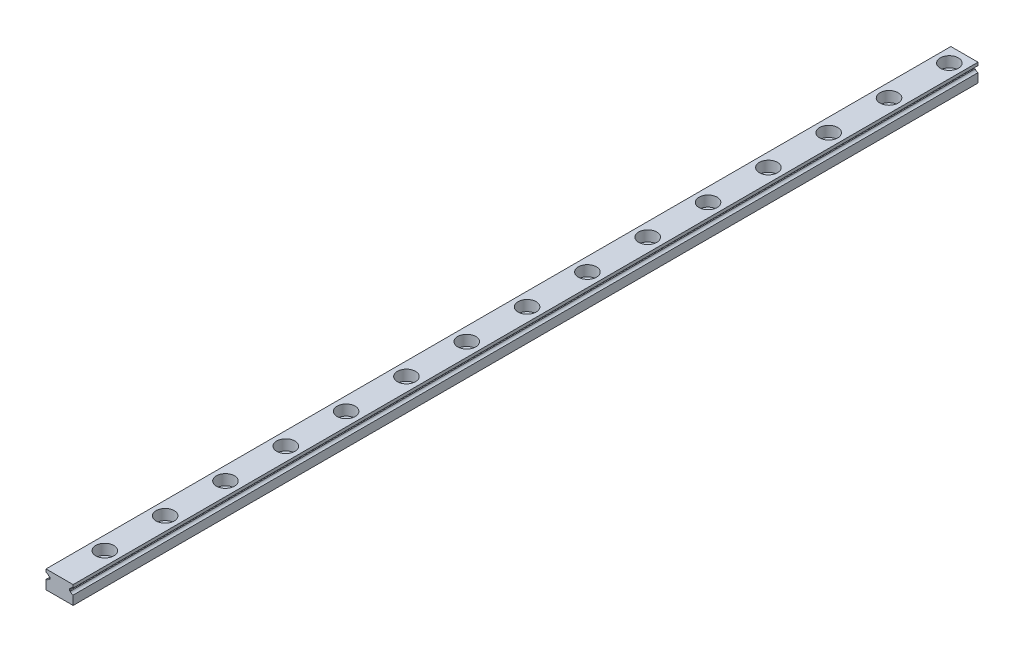
SolidWorks part; units mm, degrees
ref_plane "Спереди" through (0, 0, 0) normal (0, 0, 1) x (1, 0, 0)
ref_plane "Сверху" through (0, 0, 0) normal (0, 1, 0) x (1, 0, 0)
ref_plane "Справа" through (0, 0, 0) normal (1, 0, 0) x (0, 0, -1)
sketch "Sketch1" plane through (0, 0, 0) normal (0, 0, 1) x (1, 0, 0)
  line L0 (0, 0) -> (0, 5.7299) construction
  line L1 (-4.5, -3) -> (4.5, -3)
  line L2 (-4.5, -3) -> (-4.5, 0)
  line L3 (-4.5, 3) -> (4.5, 3)
  line L4 (4.5, -3) -> (4.5, 0)
  line L5 (-4.5, -3) -> (4.5, 3) construction
  line L6 (-4.5, 3) -> (4.5, -3) construction
  line L7 (-4.5, 2) -> (-4.5, 3)
  line L8 (-3.564, 0.648) -> (-3.2351, 0.648)
  line L9 (3.564, 0.648) -> (3.2351, 0.648)
  line L10 (-3.564, 1.352) -> (-3.2351, 1.352)
  line L11 (-3.2351, 0.648) -> (-3.2351, 1.352)
  line L12 (3.2351, 0.648) -> (3.2351, 1.352)
  line L13 (3.564, 1.352) -> (3.2351, 1.352)
  line L14 (4.5, 2) -> (4.5, 3)
  arc A0 (-3.564, 1.352) -> (-4.5, 2) centre (-4.5, 1) ccw
  arc A1 (-4.5, 0) -> (-3.564, 0.648) centre (-4.5, 1) ccw
  arc A2 (4.5, 0) -> (3.564, 0.648) centre (4.5, 1) cw
  arc A3 (3.564, 1.352) -> (4.5, 2) centre (4.5, 1) cw
  point P0 (0, 0)
  dimension "D3" = 1
  dimension "D1" = 9
  dimension "D2" = 6
  dimension "D4" = 2
extrude "Extrude1" add sketch "Sketch1" along normal blind 300
sketch "Sketch2" plane through (0, 3, 0) normal (0, 1, 0) x (1, 0, 0)
  line L0 (4.5, 0) -> (-4.5, 0) construction
  circle A0 centre (0, -5) radius 1.75
  circle A1 centre (0, -5) radius 3
  dimension "D1" = 3.5
  dimension "D2" = 6
  dimension "D3" = 5
extrude "Extrude2" cut sketch "Sketch2" against normal blind 3.5 contours A1
extrude "Extrude3" cut sketch "Sketch" against normal through all contours A0
sketch "Sketch" plane through (0, 3, 0) normal (0, 1, 0) x (1, 0, 0) same geometry as "Sketch2"
pattern_linear "LPattern1" count 15 spacing 20 along (0, 0, 1) of "Extrude2", "Extrude3"
sketch "草图1" plane through (0, 3, 0) normal (0, 1, 0) x (1, 0, 0)
  line L0 (-3.3296, -21.0573) -> (3.2415, -21.0573)
  text T0 "C."
